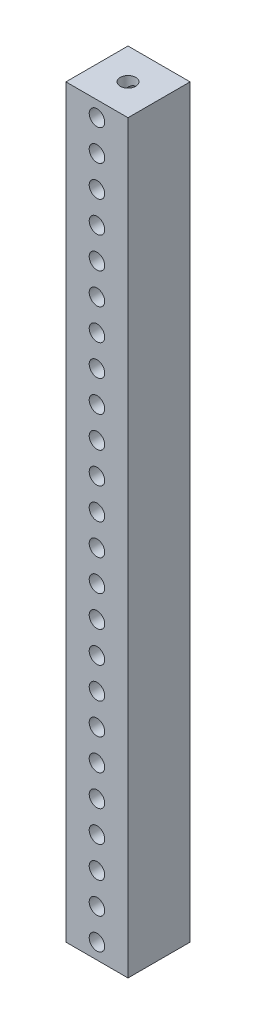
SolidWorks part; units mm, degrees
ref_plane "Front Plane" through (0, 0, 0) normal (0, 0, 1) x (1, 0, 0)
ref_plane "Top Plane" through (0, 0, 0) normal (0, 1, 0) x (1, 0, 0)
ref_plane "Right Plane" through (0, 0, 0) normal (1, 0, 0) x (0, 0, -1)
sketch "Sketch2" plane through (0, 0, 0) normal (0, 1, 0) x (1, 0, 0)
  line L1 (-10, -10) -> (10, -10)
  line L2 (-10, -10) -> (-10, 10)
  line L3 (-10, 10) -> (10, 10)
  line L4 (10, -10) -> (10, 10)
  line L5 (-10, -10) -> (10, 10) construction
  line L6 (-10, 10) -> (10, -10) construction
  circle A0 centre (0, 0) radius 2.5
  point P0 (0, 0)
  dimension "D3" = 5
  dimension "D1" = 20
  dimension "D2" = 20
extrude "Boss-Extrude1" add sketch "Sketch2" along normal blind 240
sketch "Sketch3" plane through (0, 0, 10) normal (0, 0, 1) x (1, 0, 0)
  circle A0 centre (0, 5) radius 2.5
  dimension "D1" = 5
  dimension "D2" = 5
extrude "Cut-Extrude1" cut sketch "Sketch3" against normal through all
pattern_linear "LPattern1" count 22 spacing 10 along (0, 1, 0) of "Cut-Extrude1"
sketch "Sketch4" plane through (0, 0, 10) normal (0, 0, 1) x (1, 0, 0)
  line L0 (0, -750) -> (0, 49250) construction
  line L1 (-10, 240) -> (10, 240) construction
  circle A0 centre (0, 235) radius 2.5
  circle A1 centre (0, 225) radius 2.5
  point P5 (0, 240)
  dimension "D1" = 5
  dimension "D2" = 5
  dimension "D3" = 5
  dimension "D4" = 15
extrude "Cut-Extrude2" cut sketch "Sketch4" against normal through all
